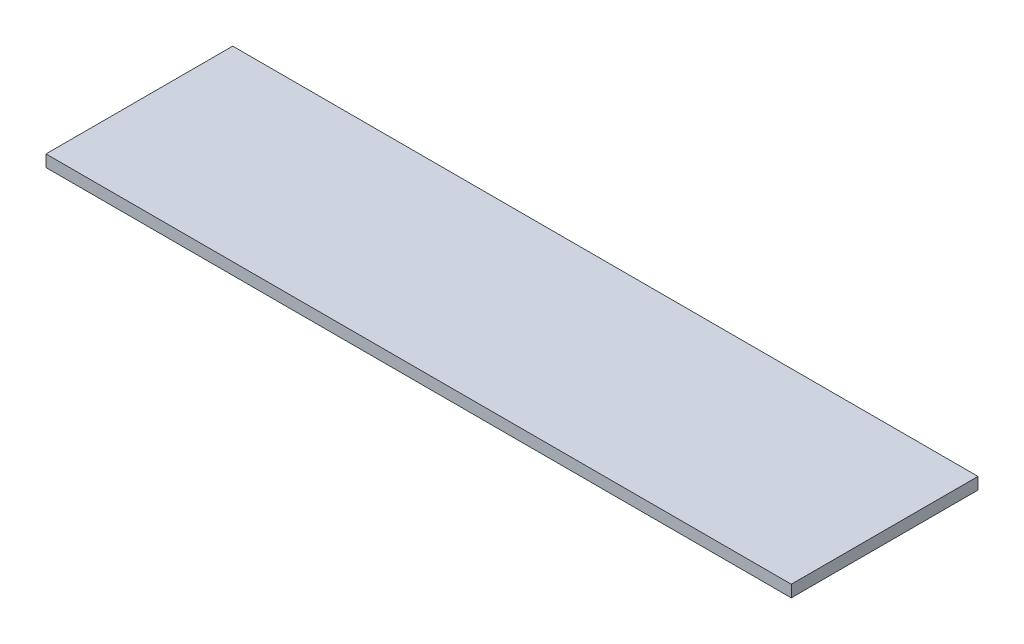
SolidWorks part; units mm, degrees
ref_plane "Front" through (0, 0, 0) normal (0, 0, 1) x (1, 0, 0)
ref_plane "Top" through (0, 0, 0) normal (0, 1, 0) x (1, 0, 0)
ref_plane "Right" through (0, 0, 0) normal (1, 0, 0) x (0, 0, -1)
sketch "Sketch1" plane through (0, 0, 0) normal (0, 1, 0) x (1, 0, 0)
  line L1 (0, 0) -> (199.58, 0)
  line L2 (0, 0) -> (0, 30)
  line L3 (0, 30) -> (199.58, 30)
  line L4 (199.58, 0) -> (199.58, 30)
  dimension "D1" = 199.58
  dimension "D2" = 30
extrude "Boss-Extrude1" add sketch "Sketch1" along normal blind 3.175 contours L3 | L1 L4 L3 L2 region at (99.79, 0, -15)
sketch "Sketch2" plane through (0, 0, -30) normal (0, 0, -1) x (-1, 0, 0)
  line L1 (-199.58, 0) -> (0, 0)
  line L2 (-199.58, 0) -> (-199.58, 3.175)
  line L3 (-199.58, 3.175) -> (0, 3.175)
  line L4 (0, 0) -> (0, 3.175)
extrude "Boss-Extrude2" add sketch "Sketch2" along normal blind 20
